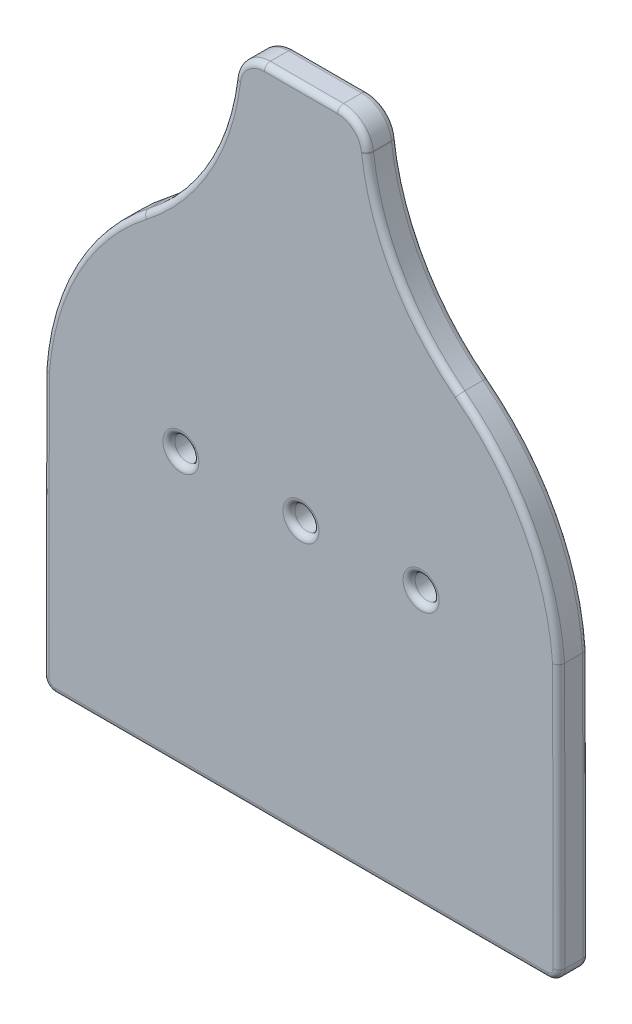
SolidWorks part; units mm, degrees
ref_plane "Front Plane" through (0, 0, 0) normal (0, 0, 1) x (1, 0, 0)
ref_plane "Top Plane" through (0, 0, 0) normal (0, 1, 0) x (1, 0, 0)
ref_plane "Right Plane" through (0, 0, 0) normal (1, 0, 0) x (0, 0, -1)
sketch "Sketch2" plane through (0, 0, 0) normal (0, 0, 1) x (1, 0, 0)
  line L0 (-21.4476, 11.4999) -> (-21.5, -11.5)
  line L5 (0, 42.6667) -> (0, -17.9649) construction
  line L6 (-3.0476, 42.6667) -> (3.0476, 42.6667)
  line L7 (21.5, -11.5) -> (-21.5, -11.5)
  line L8 (21.4476, 11.4999) -> (21.5, -11.5)
  line L9 (5.5295, 40.4672) -> (5.5348, 40.4229)
  line L10 (-5.5295, 40.4672) -> (-5.5348, 40.4229)
  arc A1 (21.4476, 11.4999) -> (13.1538, 27.0067) centre (0, 10) ccw
  arc A2 (-13.1538, 27.0067) -> (-21.4476, 11.4999) centre (0, 10) ccw
  arc A3 (5.5348, 40.4229) -> (13.1538, 27.0067) centre (25.3898, 42.8269) ccw
  arc A4 (-5.5348, 40.4229) -> (-13.1538, 27.0067) centre (-25.3898, 42.8269) cw
  arc A5 (-5.5295, 40.4672) -> (-3.0476, 42.6667) centre (-3.0476, 40.1667) cw
  arc A6 (3.0476, 42.6667) -> (5.5295, 40.4672) centre (3.0476, 40.1667) cw
  point P0 (0, 0)
  point P15 (6.7467, 30.414)
  point P18 (-6.7467, 30.414)
  point P21 (-5.2632, 42.6667)
  point P24 (5.2632, 42.6667)
  dimension "D3" = 20
  dimension "D4" = 2.5
  dimension "D1" = 23
  dimension "D2" = 23
extrude "Boss-Extrude1" add sketch "Sketch2" along normal blind 2.5 contours A4 A2 L0 L7 L8 A1 A3 L9 A6 L6 A5 L10
sketch "Sketch3" plane through (0, 0, 2.5) normal (0, 0, 1) x (1, 0, 0)
  circle A0 centre (0, 11.3012) radius 1
  circle A1 centre (10, 11.3012) radius 1
  circle A2 centre (-10, 11.3012) radius 1
  dimension "D1" = 2
  dimension "D2" = 2
  dimension "D3" = 2
  dimension "D4" = 10
  dimension "D5" = 10
  dimension "D6" = 0
extrude "Cut-Extrude1" cut sketch "Sketch3" against normal blind 2.5
fillet "Fillet1" radius 1 2 edges at (-21.5, -11.5, 1.25) (21.5, -11.5, 1.25)
fillet "Fillet2" radius 0.5 17 edges at (-18.9586, 20.1401, 2.5) (-7.9985, 32.9505, 2.5) (-5.5322, 40.445, 2.5) (-4.7057, 42.0377, 2.5) (0, 42.6667, 2.5) (4.7057, 42.0377, 2.5) (5.5322, 40.445, 2.5) (7.9985, 32.9505, 2.5) (18.9586, 20.1401, 2.5) (21.4727, 0.5011, 2.5) (21.2056, -11.2063, 2.5) (0, -11.5, 2.5) (-21.2056, -11.2063, 2.5) (-21.4727, 0.5011, 2.5) (1, 11.3012, 2.5) (11, 11.3012, 2.5) (-9, 11.3012, 2.5)
fillet "Fillet3" radius 0.5 17 edges at (21.2056, -11.2063, 0) (21.4727, 0.5011, 0) (18.9586, 20.1401, 0) (7.9985, 32.9505, 0) (5.5322, 40.445, 0) (4.7057, 42.0377, 0) (0, 42.6667, 0) (-4.7057, 42.0377, 0) (-5.5322, 40.445, 0) (-7.9985, 32.9505, 0) (-18.9586, 20.1401, 0) (-21.4727, 0.5011, 0) (-21.2056, -11.2063, 0) (0, -11.5, 0) (1, 11.3012, 0) (11, 11.3012, 0) (-9, 11.3012, 0)
